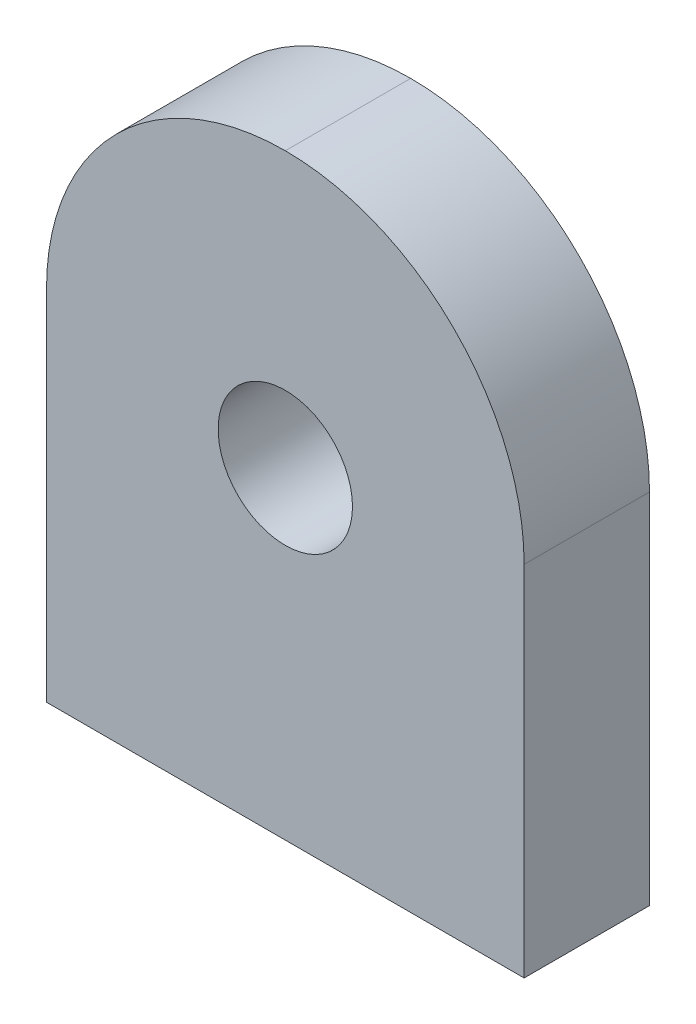
SolidWorks part; units mm, degrees
ref_plane "Front Plane" through (0, 0, 0) normal (0, 0, 1) x (1, 0, 0)
ref_plane "Top Plane" through (0, 0, 0) normal (0, 1, 0) x (1, 0, 0)
ref_plane "Right Plane" through (0, 0, 0) normal (1, 0, 0) x (0, 0, -1)
sketch "Sketch1" plane through (0, 0, 0) normal (0, 0, 1) x (1, 0, 0)
  line L1 (0, 0) -> (16, 0)
  line L2 (0, 0) -> (0, 20)
  line L3 (0, 20) -> (16, 20)
  line L4 (16, 0) -> (16, 20)
  dimension "D1" = 16
  dimension "D2" = 20
extrude "Boss-Extrude1" add sketch "Sketch1" along normal blind 4.2
sketch "Sketch2" plane through (0, 0, 4.2) normal (0, 0, 1) x (1, 0, 0)
  line L0 (8, 0) -> (8, 20) construction
  line L1 (0, 0) -> (16, 0) construction
  line L2 (16, 20) -> (0, 20) construction
  circle A0 centre (8, 10.8) radius 2.25
  dimension "D1" = 4.5
  dimension "D2" = 10.8
extrude "Cut-Extrude1" cut sketch "Sketch2" against normal through all
fillet "Fillet1" radius 8 2 edges at (16, 20, 2.1) (0, 20, 2.1)
